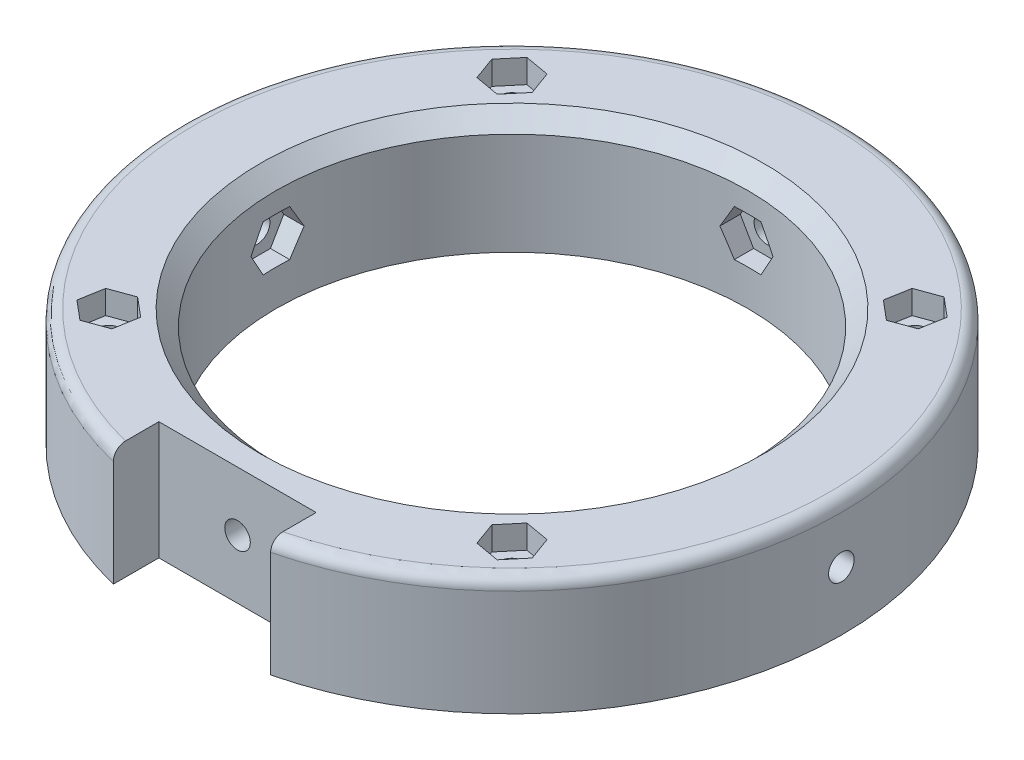
SolidWorks part; units mm, degrees
ref_plane "Front" through (0, 0, 0) normal (0, 0, 1) x (1, 0, 0)
ref_plane "Top" through (0, 0, 0) normal (0, 1, 0) x (1, 0, 0)
ref_plane "Right" through (0, 0, 0) normal (1, 0, 0) x (0, 0, -1)
sketch "Sketch1" plane through (0, 0, 0) normal (0, 1, 0) x (1, 0, 0)
  circle A0 centre (0, 0) radius 41.9
  dimension "D1" = 83.8
extrude "Top-Part" add sketch "Sketch1" along normal blind 15
sketch "Sketch2" plane through (0, 15, 0) normal (0, 1, 0) x (1, 0, 0)
  circle A0 centre (0, 0) radius 30
  dimension "D1" = 60
extrude "Cut-Extrude1" cut sketch "Sketch2" against normal blind 20
fillet "Fillet1" radius 1.5 1 edges at (0, 15, 41.9)
chamfer "Chamfer1" distance 2 angle 45 1 edges at (0, 15, 30)
sketch "Sketch8" plane through (0, 15, 0) normal (0, 1, 0) x (1, 0, 0)
  line L0 (0, 0) -> (0, 52.711) construction
  line L1 (25.0832, 22.5168) -> (28.0563, 23.5989)
  line L8 (0, 0) -> (-43.3951, 43.3951) construction
  line L9 (-25.6326, 25.6326) -> (-25.6326, 34.5059) construction
  line L10 (-22.5168, 25.0832) -> (-23.5989, 28.0563)
  line L11 (-23.5989, 28.0563) -> (-26.7147, 28.6057)
  line L12 (-26.7147, 28.6057) -> (-28.7485, 26.182)
  line L13 (-28.7485, 26.182) -> (-27.6663, 23.2089)
  line L14 (-27.6663, 23.2089) -> (-24.5505, 22.6595)
  line L15 (-24.5505, 22.6595) -> (-22.5168, 25.0832)
  line L16 (28.0563, 23.5989) -> (28.6057, 26.7147)
  line L17 (28.6057, 26.7147) -> (26.182, 28.7485)
  line L18 (26.182, 28.7485) -> (23.2089, 27.6663)
  line L19 (23.2089, 27.6663) -> (22.6595, 24.5505)
  line L20 (22.6595, 24.5505) -> (25.0832, 22.5168)
  line L21 (0, 0) -> (43.3951, 43.3951) construction
  line L23 (22.5168, -25.0832) -> (23.5989, -28.0563)
  line L24 (23.5989, -28.0563) -> (26.7147, -28.6057)
  line L25 (26.7147, -28.6057) -> (28.7485, -26.182)
  line L26 (28.7485, -26.182) -> (27.6663, -23.2089)
  line L27 (27.6663, -23.2089) -> (24.5505, -22.6595)
  line L28 (24.5505, -22.6595) -> (22.5168, -25.0832)
  line L29 (0, 0) -> (43.3951, -43.3951) construction
  line L31 (-25.0832, -22.5168) -> (-28.0563, -23.5989)
  line L32 (-28.0563, -23.5989) -> (-28.6057, -26.7147)
  line L33 (-28.6057, -26.7147) -> (-26.182, -28.7485)
  line L34 (-26.182, -28.7485) -> (-23.2089, -27.6663)
  line L35 (-23.2089, -27.6663) -> (-22.6595, -24.5505)
  line L36 (-22.6595, -24.5505) -> (-25.0832, -22.5168)
  line L37 (0, 0) -> (-43.3951, -43.3951) construction
  line L39 (-25.6326, 25.6326) -> (-27.9138, 12.6954) construction
  circle A0 centre (0, 0) radius 36.25 construction
  circle A1 centre (25.6326, 25.6326) radius 2.74 construction
  circle A2 centre (-25.6326, 25.6326) radius 2.74 construction
  circle A3 centre (25.6326, -25.6326) radius 2.74 construction
  circle A4 centre (-25.6326, -25.6326) radius 2.74 construction
  circle A5 centre (-25.6326, 25.6326) radius 1.625
  circle A6 centre (25.6326, 25.6326) radius 1.625
  circle A7 centre (25.6326, -25.6326) radius 1.625
  circle A8 centre (-25.6326, -25.6326) radius 1.625
  point P8 (25.6326, 25.6326)
  point P10 (28.331, 25.1568)
  point P18 (-25.6326, 25.6326)
  point P20 (-25.1568, 28.331)
  point P36 (25.6326, -25.6326)
  point P38 (25.1568, -28.331)
  point P50 (-25.6326, -25.6326)
  point P52 (-28.331, -25.1568)
  point P63 (0, 0)
  point P69 (-27.8231, 23.2366)
  dimension "D1" = 72.5
  dimension "D5" = 3.25
  dimension "D2" = 4
  dimension "D3" = 45
  dimension "D4" = 10
  dimension "D6" = 5.75
extrude "Cut-Extrude8" cut sketch "Sketch8<7>" against normal blind 3
sketch "Sketch8<7>" plane through (0, 15, 0) normal (0, 1, 0) x (1, 0, 0) same geometry as "Sketch8"
extrude "Cut-Extrude7" cut sketch "Sketch8" against normal through all contours A5 | A6 | A7 | A8
sketch "Sketch13" plane through (0, 0, 0) normal (0, -1, 0) x (1, 0, 0)
  line L0 (0, 0) -> (0, 66.0162) construction
  line L1 (-10, 35.5191) -> (-10, 40.6892)
  line L2 (10, 35.5191) -> (10, 40.6892)
  line L3 (-10, 40.6892) -> (10, 35.5191) construction
  line L4 (10, 40.6892) -> (-10, 35.5191) construction
  circle A0 centre (0, 0) radius 41.9 construction
  arc A1 (10, 40.6892) -> (-10, 40.6892) centre (0, 0) ccw
  arc A2 (10, 35.5191) -> (-10, 35.5191) centre (0, 0) ccw
  point P6 (0, 38.1042)
  point P10 (0, 36.9)
  point P12 (0, 41.9)
  dimension "D1" = 10
  dimension "D3" = 5
extrude "Cut-Extrude11" cut sketch "Sketch13" against normal through all
ref_plane "Plane2" through (0, 0, 41.9) normal (0, 0, 1) x (1, 0, 0)
ref_plane "Plane3" through (0, 0, 32.4) normal (0, 0, 1) x (1, 0, 0)
sketch "Sketch15" plane through (0, 0, 32.4) normal (0, 0, 1) x (1, 0, 0)
  line L0 (0, -23.0183) -> (0, 33.1182) construction
  circle A1 centre (0, 7.5) radius 1.625
  point P11 (0, 7.5)
  dimension "D3" = 3.25
  dimension "D1" = 7.5
extrude "Cut-Extrude14" cut sketch "Sketch15" against normal blind 10 and the other way blind 10
sketch "Sketch16" plane through (0, 0, 32.4) normal (0, 0, 1) x (1, 0, 0)
  line L0 (0, 0) -> (0, 26.985) construction
  line L2 (3.3775, 7.5) -> (1.6887, 10.425)
  line L3 (1.6887, 10.425) -> (-1.6887, 10.425)
  line L4 (-1.6887, 10.425) -> (-3.3775, 7.5)
  line L5 (-3.3775, 7.5) -> (-1.6887, 4.575)
  line L6 (-1.6887, 4.575) -> (1.6887, 4.575)
  line L7 (1.6887, 4.575) -> (3.3775, 7.5)
  circle A0 centre (0, 7.5) radius 2.925 construction
  point P4 (0, 4.575)
  point P13 (0, 10.425)
  dimension "D1" = 5.85
  dimension "D2" = 7.5
extrude "Cut-Extrude15" cut sketch "Sketch16" against normal blind 10
pattern_circular "CirPattern1" count 4 over 360 about axis through (0, 0, 0) along (0, 1, 0) of "Cut-Extrude14"
pattern_circular "CirPattern2" count 4 every 90 about axis through (0, 0, 0) along (0, 1, 0) of "Cut-Extrude15"
sketch "Sketch3" plane through (0, 0, 0) normal (0, -1, 0) x (1, 0, 0)
  circle A0 centre (0, 0) radius 41.9
  dimension "D1" = 83.8
extrude "Bottom-Part" add sketch "Sketch3" along normal blind 20 separate body
ref_plane "Plane1" through (0, -1.5, 0) normal (0, 1, 0) x (1, 0, 0)
sketch "Sketch6" plane through (0, -1.5, 0) normal (0, 1, 0) x (1, 0, 0)
  line L0 (0, 0) -> (-97.4577, 0) construction
  line L5 (-37.9, 0) -> (-41.9, 0) construction
  circle A0 centre (0, 0) radius 37.9
  circle A1 centre (0, 0) radius 41.9 construction
  circle A2 centre (0, 0) radius 41.9 construction
  point P6 (-37.9, 0)
  point P9 (-41.9, 0)
  dimension "D1" = 4
extrude "Cut-Extrude3" cut sketch "Sketch6" against normal through all
sketch "ｽｹｯﾁ1" plane through (0, 0, 0) normal (0, 1, 0) x (1, 0, 0)
  line L3 (21.5, -21.5) -> (-21.5, -21.5)
  line L4 (21.5, -21.5) -> (21.5, 21.5)
  line L5 (21.5, 21.5) -> (-21.5, 21.5)
  line L6 (-21.5, -21.5) -> (-21.5, 21.5)
  line L7 (21.5, -21.5) -> (-21.5, 21.5) construction
  line L8 (21.5, 21.5) -> (-21.5, -21.5) construction
  point P2 (0, 0)
  dimension "D1" = 43
extrude "ﾎﾞｽ - 押し出し1" add sketch "ｽｹｯﾁ1" along normal blind 8
fillet "ﾌｨﾚｯﾄ1" radius 5 4 edges at (21.5, 4, -21.5) (-21.5, 4, -21.5) (-21.5, 4, 21.5) (21.5, 4, 21.5)
sketch "Sketch7" plane through (0, -1.5, 0) normal (0, 1, 0) x (1, 0, 0)
  circle A0 centre (0, 0) radius 17.5
  circle A1 centre (17, -17) radius 1
  circle A2 centre (-17, -17) radius 1
  circle A3 centre (-17, 17) radius 1
  circle A4 centre (17, 17) radius 1
  dimension "D1" = 35
  dimension "D2" = 2
extrude "Cut-Extrude4" cut sketch "Sketch7" against normal through all and the other way through all
sketch "Sketch12" plane through (0, -1.5, 0) normal (0, -1, 0) x (1, 0, 0)
  line L1 (19.75, -19.75) -> (-19.75, -19.75)
  line L2 (19.75, -19.75) -> (19.75, 19.75)
  line L3 (19.75, 19.75) -> (-19.75, 19.75)
  line L4 (-19.75, -19.75) -> (-19.75, 19.75)
  line L5 (19.75, -19.75) -> (-19.75, 19.75) construction
  line L6 (19.75, 19.75) -> (-19.75, -19.75) construction
  point P0 (0, 0)
  dimension "D1" = 39.5
extrude "Cut-Extrude10" cut sketch "Sketch12" against normal blind 8.5
fillet "Fillet3" radius 2 4 edges at (-19.75, 2.75, -19.75) (-19.75, 2.75, 19.75) (19.75, 2.75, -19.75) (19.75, 2.75, 19.75)
sketch "Sketch17" plane through (0, -1.5, 0) normal (0, -1, 0) x (1, 0, 0)
  circle A0 centre (25.6326, -25.6326) radius 1.625 construction
  circle A1 centre (-25.6326, -25.6326) radius 1.625 construction
  circle A2 centre (25.6326, 25.6326) radius 1.625 construction
  circle A3 centre (-25.6326, 25.6326) radius 1.625 construction
  circle A4 centre (25.6326, -25.6326) radius 1.625
  circle A5 centre (-25.6326, -25.6326) radius 1.625
  circle A6 centre (25.6326, 25.6326) radius 1.625
  circle A7 centre (-25.6326, 25.6326) radius 1.625
extrude "Cut-Extrude16" cut sketch "Sketch17" against normal through all
sketch "Sketch18" plane through (0, -1.5, 0) normal (0, -1, 0) x (1, 0, 0)
  circle A0 centre (-25.6326, 25.6326) radius 3
  circle A1 centre (25.6326, 25.6326) radius 3
  circle A2 centre (25.6326, -25.6326) radius 3
  circle A3 centre (-25.6326, -25.6326) radius 3
  dimension "D1" = 6
extrude "Cut-Extrude17" cut sketch "Sketch18" along normal through all
sketch "Sketch19" plane through (0, -1.5, 0) normal (0, -1, 0) x (1, 0, 0)
  line L0 (-6, 33) -> (-6, 37.4221)
  line L1 (6, 33) -> (6, 37.4221)
  line L2 (33, 6) -> (37.4221, 6)
  line L3 (33, -6) -> (37.4221, -6)
  line L4 (6, -33) -> (6, -37.4221)
  line L5 (-6, -33) -> (-6, -37.4221)
  line L6 (-33, -6) -> (-37.4221, -6)
  line L7 (-33, 6) -> (-37.4221, 6)
  arc A0 (-6, 33) -> (6, 33) centre (0, 33) ccw
  arc A1 (24.9276, 28.5486) -> (-24.9276, 28.5486) centre (0, 0) ccw construction
  arc A2 (24.9276, 28.5486) -> (-24.9276, 28.5486) centre (0, 0) ccw construction
  arc A3 (6, 37.4221) -> (-6, 37.4221) centre (0, 0) ccw
  arc A4 (37.4221, -6) -> (37.4221, 6) centre (0, 0) ccw
  arc A5 (33, 6) -> (33, -6) centre (33, 0) ccw
  arc A6 (-6, -37.4221) -> (6, -37.4221) centre (0, 0) ccw
  arc A7 (6, -33) -> (-6, -33) centre (0, -33) ccw
  arc A8 (-37.4221, 6) -> (-37.4221, -6) centre (0, 0) ccw
  arc A9 (-33, -6) -> (-33, 6) centre (-33, 0) ccw
  circle A10 centre (0, 33) radius 2.75
  circle A11 centre (33, 0) radius 2.75
  circle A12 centre (0, -33) radius 2.75
  circle A13 centre (-33, 0) radius 2.75
  dimension "D1" = 12
  dimension "D4" = 4
  dimension "D2" = 33
  dimension "D3" = 4
extrude "Boss-Extrude1" add sketch "Sketch19" along normal up to surface (18.5 mm away) up to face at (0, -20, 0)
sketch "Sketch20" plane through (0, -20, 0) normal (0, -1, 0) x (1, 0, 0)
  line L1 (-43.8995, -46.5498) -> (43.8995, -46.5498)
  line L2 (-43.8995, -46.5498) -> (-43.8995, 46.5498)
  line L3 (-43.8995, 46.5498) -> (43.8995, 46.5498)
  line L4 (43.8995, -46.5498) -> (43.8995, 46.5498)
  line L5 (-43.8995, -46.5498) -> (43.8995, 46.5498) construction
  line L6 (-43.8995, 46.5498) -> (43.8995, -46.5498) construction
  point P0 (0, 0)
extrude "Cut-Extrude18" cut sketch "Sketch20" against normal blind 10
sketch "Sketch21" plane through (0, 15, 0) normal (0, 1, 0) x (1, 0, 0)
  line L1 (-10, -34.9) -> (10, -34.9)
  line L2 (-10, -34.9) -> (-10, -43.5518)
  line L3 (-10, -43.5518) -> (10, -43.5518)
  line L4 (10, -34.9) -> (10, -43.5518)
  dimension "D1" = 34.9
extrude "Cut-Extrude19" cut sketch "Sketch21" against normal up to surface (15 mm away) up to face at (-25.6326, 0, -27.2576)
sketch "Sketch23" plane through (0, 15, 0) normal (0, 1, 0) x (1, 0, 0)
  circle A0 centre (0, 0) radius 30
extrude "Cut-Extrude21" cut sketch "Sketch23" against normal through all
sketch "Sketch24" plane through (0, -10, 0) normal (0, -1, 0) x (1, 0, 0)
  circle A0 centre (0, 0) radius 41.9
extrude "Cut-Extrude22" cut sketch "Sketch24" against normal up to surface (10 mm away) up to face at (0, 0, -30)
